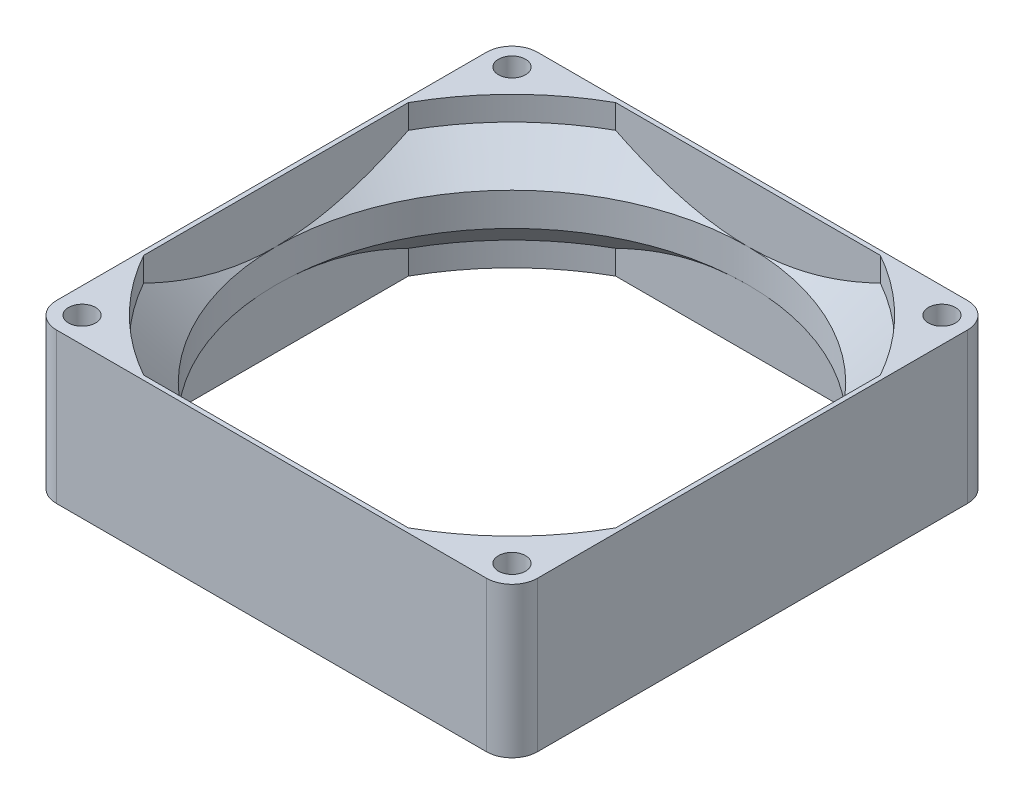
SolidWorks part; units mm, degrees
ref_plane "Front Plane" through (0, 0, 0) normal (0, 0, 1) x (1, 0, 0)
ref_plane "Top Plane" through (0, 0, 0) normal (0, 1, 0) x (1, 0, 0)
ref_plane "Right Plane" through (0, 0, 0) normal (1, 0, 0) x (0, 0, -1)
sketch "Sketch1" plane through (0, 0, 0) normal (0, 1, 0) x (1, 0, 0)
  line L0 (22.0099, 39.25) -> (-22.0099, 39.25)
  line L1 (-35.75, -40) -> (35.75, -40)
  line L2 (-40, -35.75) -> (-40, 35.75)
  line L3 (-35.75, 40) -> (35.75, 40)
  line L4 (40, -35.75) -> (40, 35.75)
  line L5 (-40, -40) -> (40, 40) construction
  line L6 (-40, 40) -> (40, -40) construction
  line L7 (39.25, -22.0099) -> (39.25, 22.0099)
  line L8 (-22.0099, -39.25) -> (22.0099, -39.25)
  line L9 (-39.25, 22.0099) -> (-39.25, -22.0099)
  arc A0 (22.0099, 39.25) -> (39.25, 22.0099) centre (0, 0) cw
  arc A1 (39.25, -22.0099) -> (22.0099, -39.25) centre (0, 0) cw
  arc A2 (-22.0099, -39.25) -> (-39.25, -22.0099) centre (0, 0) cw
  arc A3 (-39.25, 22.0099) -> (-22.0099, 39.25) centre (0, 0) cw
  circle A4 centre (35.75, 35.75) radius 2.25
  circle A5 centre (35.75, -35.75) radius 2.25
  circle A6 centre (-35.75, -35.75) radius 2.25
  circle A7 centre (-35.75, 35.75) radius 2.25
  arc A8 (-35.75, -40) -> (-40, -35.75) centre (-35.75, -35.75) cw
  arc A9 (35.75, -40) -> (40, -35.75) centre (35.75, -35.75) ccw
  arc A10 (35.75, 40) -> (40, 35.75) centre (35.75, 35.75) cw
  arc A11 (-40, 35.75) -> (-35.75, 40) centre (-35.75, 35.75) cw
  point P0 (0, 0)
  point P22 (0, 0)
  point P27 (0, 0)
  dimension "D2" = 45
  dimension "D5" = 4.5
  dimension "D1" = 80
  dimension "D3" = 39.25
  dimension "D7" = 71.5
  dimension "D4" = 4
  dimension "D6" = 4
extrude "Boss-Extrude1" add sketch "Sketch1" along normal blind 25
sketch "Sketch2" plane through (0, 0, 0) normal (1, 0, 0) x (0, 0, -1)
  line L0 (0, 0) -> (0, 29.5169) construction
  line L1 (39.25, 15.25) -> (45, 21)
  line L2 (39.25, 25) -> (39.25, 0) construction
  line L3 (39.25, 15.25) -> (39.25, 9.75)
  line L4 (45, 21) -> (45, 4)
  line L5 (45, 4) -> (39.25, 9.75)
  line L6 (-35.75, 25) -> (35.75, 25) construction
  line L7 (-35.75, 0) -> (35.75, 0) construction
  line L8 (-35.75, 25) -> (35.75, 25)
  line L9 (-35.75, 0) -> (35.75, 0)
  line L10 (39.25, 12.5) -> (45, 12.5) construction
  dimension "D1" = 45
  dimension "D2" = 4
  dimension "D3" = 45
revolve "Revolve1" add sketch "Sketch2" angle 360 about L0 region at (0, 12.5, -42.6148)
sketch "Sketch3" plane through (0, 0, 0) normal (0, 1, 0) x (1, 0, 0)
  line L0 (-40, 35.75) -> (-40, -35.75) construction
  line L1 (-40, 35.75) -> (-40, -35.75)
  line L2 (-35.75, -40) -> (35.75, -40) construction
  line L3 (40, -35.75) -> (40, 35.75) construction
  line L4 (35.75, 40) -> (-35.75, 40) construction
  line L5 (-35.75, -40) -> (35.75, -40)
  line L6 (40, -35.75) -> (40, 35.75)
  line L7 (35.75, 40) -> (-35.75, 40)
  arc A0 (-40, -35.75) -> (-35.75, -40) centre (-35.75, -35.75) ccw construction
  arc A1 (35.75, -40) -> (40, -35.75) centre (35.75, -35.75) ccw construction
  arc A2 (40, 35.75) -> (35.75, 40) centre (35.75, 35.75) ccw construction
  arc A3 (-40, -35.75) -> (-35.75, -40) centre (-35.75, -35.75) ccw
  arc A4 (35.75, -40) -> (40, -35.75) centre (35.75, -35.75) ccw
  arc A5 (40, 35.75) -> (35.75, 40) centre (35.75, 35.75) ccw
  arc A6 (-35.75, 40) -> (-40, 35.75) centre (-35.75, 35.75) ccw construction
  arc A7 (-35.75, 40) -> (-40, 35.75) centre (-35.75, 35.75) ccw
  circle A8 centre (0, 0) radius 54.8081
extrude "Cut-Extrude1" cut sketch "Sketch3" against normal through all both and the other way through all contours A7 A8 A3 L1 | A3 A8 A4 L5 | A4 A8 A5 L6 | A5 A8 A7 L7 region at (-45.9916, 0, 0) region at (0, 0, -45.9916) region at (0, 0, 45.9916) region at (45.9916, 0, 0)
